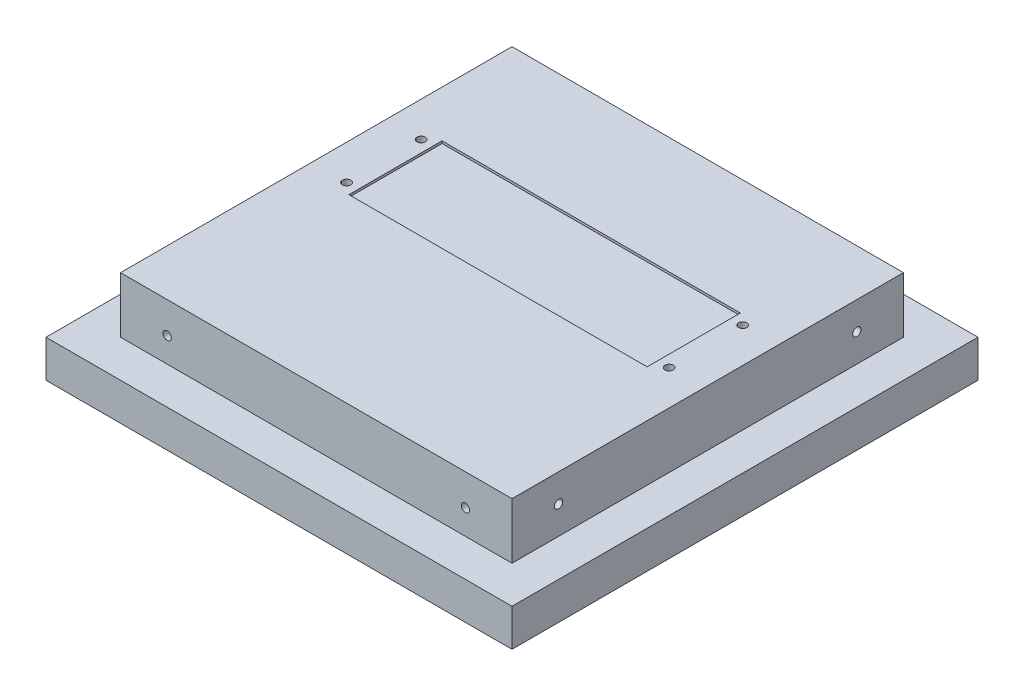
SolidWorks part; units mm, degrees
ref_plane "Front Plane" through (0, 0, 0) normal (0, 0, 1) x (1, 0, 0)
ref_plane "Top Plane" through (0, 0, 0) normal (0, 1, 0) x (1, 0, 0)
ref_plane "Right Plane" through (0, 0, 0) normal (1, 0, 0) x (0, 0, -1)
sketch "Sketch1" plane through (0, 0, 0) normal (0, 1, 0) x (1, 0, 0)
  line L1 (-50, 50) -> (50, 50)
  line L2 (-50, 50) -> (-50, -50)
  line L3 (-50, -50) -> (50, -50)
  line L4 (50, 50) -> (50, -50)
  line L5 (-50, 50) -> (50, -50) construction
  line L6 (-50, -50) -> (50, 50) construction
  point P0 (0, 0)
  dimension "D1" = 100
extrude "Boss-Extrude2" add sketch "Sketch1" along normal blind 8
sketch "Sketch2" plane through (0, 8, 0) normal (0, 1, 0) x (1, 0, 0)
  line L1 (-42, 42) -> (42, 42)
  line L2 (-42, 42) -> (-42, -42)
  line L3 (-42, -42) -> (42, -42)
  line L4 (42, 42) -> (42, -42)
  line L5 (-42, 42) -> (42, -42) construction
  line L6 (-42, -42) -> (42, 42) construction
  point P0 (0, 0)
extrude "Boss-Extrude3" add sketch "Sketch2" along normal blind 12
sketch "Sketch3" plane through (0, 20, 0) normal (0, 1, 0) x (1, 0, 0)
  line L0 (37, 37) -> (37, 32) construction
  line L1 (37, -37) -> (-37, -37)
  line L2 (37, -37) -> (37, 37)
  line L3 (37, 37) -> (-37, 37)
  line L4 (-37, -37) -> (-37, 37)
  line L5 (37, -37) -> (-37, 37) construction
  line L6 (37, 37) -> (-37, -37) construction
  line L7 (37, 32) -> (-37, 32) construction
  line L8 (-37, 32) -> (-37, 37) construction
  line L9 (37, 32) -> (37, 22) construction
  line L10 (37, 22) -> (-37, 22) construction
  line L11 (-37, 22) -> (-37, 32) construction
  line L12 (37, 22) -> (37, -8) construction
  line L13 (37, -8) -> (-37, -8) construction
  line L14 (-37, -8) -> (-37, 22) construction
  line L15 (37, -8) -> (32, -8) construction
  line L16 (32, -8) -> (32, 22) construction
  line L17 (-37, -8) -> (-32, -8) construction
  line L18 (-32, -8) -> (-32, 22) construction
  line L19 (32, -8) -> (32, -3) construction
  line L20 (32, -3) -> (-32, -3) construction
  line L21 (-32, 22) -> (-32, 17) construction
  line L22 (-32, 17) -> (32, 17) construction
  line L24 (32, -3) -> (-32, -3)
  line L25 (32, -3) -> (32, 17)
  line L26 (32, 17) -> (-32, 17)
  line L27 (-32, -3) -> (-32, 17)
  line L28 (32, 22) -> (34.5, 22) construction
  line L29 (-32, 22) -> (-34.5, 22) construction
  line L30 (34.5, -7.7713) -> (34.5, -0.7713) construction
  line L31 (34.5, 22) -> (34.5, 15) construction
  line L33 (-34.5, 22) -> (-34.5, 15) construction
  line L34 (-34.5, -8) -> (-34.5, -1) construction
  point P0 (0, 0)
extrude "Cut-Extrude1" cut sketch "Sketch3" against normal blind 0.5 contours L25 L24 L27 L26
hole_wizard "#2-56 Tapped Hole1" positions "3DSketch1" profile "Sketch4" tap size "#2-56" standard "ANSI Inch"
sketch3d "3DSketch1"
  point P0 (34.5, 20, 0.7713)
  point P3 (34.5, 20, -15)
  point P6 (-34.5, 20, -15)
  point P9 (-34.5, 20, 1)
sketch "Sketch4" plane through (34.5, 20, 0.7713) normal (1, 0, 0) x (0, 0, 1)
  line L0 (0, 0) -> (0, 15.5342)
  line L1 (0, 15.5342) -> (0.889, 15)
  line L2 (0.889, 15) -> (0.889, 0)
  line L5 (0.889, 0) -> (0, 0)
  line L10 (0, 15.5342) -> (-0.889, 15) construction
  line L11 (0, -6.35) -> (0, 107.95) construction
  dimension "Tap Drill Dia." = 1.778
  dimension "Tap Drill Depth" = 15
  dimension "Drill Angle" = 118
cosmetic thread "Hole Thread1" parameters "D1"=12, "D2"=2.1844
cosmetic thread "Hole Thread2" parameters "D1"=12, "D2"=2.1844
cosmetic thread "Hole Thread3" parameters "D1"=12, "D2"=2.1844
cosmetic thread "Hole Thread4" parameters "D1"=12, "D2"=2.1844
sketch "Sketch5" plane through (42, 0, 0) normal (1, 0, 0) x (0, 0, -1)
  line L0 (-42, 20) -> (42, 8) construction
  line L1 (42, 8) -> (42, 20) construction
  line L2 (42, 20) -> (-42, 8) construction
  line L3 (-42, 8) -> (-42, 20) construction
  line L4 (42, 14) -> (32, 14) construction
  line L5 (-42, 14) -> (-32, 14) construction
sketch "Sketch6" plane through (0, 0, -42) normal (0, 0, -1) x (-1, 0, 0)
  line L0 (-42, 20) -> (42, 8) construction
  line L1 (42, 8) -> (42, 20) construction
  line L2 (42, 20) -> (-42, 8) construction
  line L3 (-42, 8) -> (-42, 20) construction
  line L4 (-42, 14) -> (-32, 14) construction
  line L5 (42, 13.3038) -> (32, 13.3038) construction
sketch "Sketch7" plane through (-42, 0, 0) normal (-1, 0, 0) x (0, 0, 1)
  line L0 (-42, 20) -> (42, 8) construction
  line L1 (42, 8) -> (42, 20) construction
  line L2 (42, 13.3038) -> (32, 13.3038) construction
  line L3 (-42, 13.3038) -> (-32, 13.3038) construction
sketch "Sketch8" plane through (0, 0, 42) normal (0, 0, 1) x (1, 0, 0)
  line L0 (-42, 13.3038) -> (-32, 13.3038) construction
  line L1 (42, 13.3038) -> (32, 13.3038) construction
  line L2 (42, 20) -> (42, 8) construction
hole_wizard "#2-56 Tapped Hole2" positions "3DSketch2" profile "Sketch9" tap size "#2-56" standard "ANSI Inch"
sketch3d "3DSketch2"
  point P0 (-32, 13.3038, 42)
  point P3 (-42, 13.3038, 32)
  point P6 (32, 13.3038, 42)
sketch "Sketch9" plane through (-32, 13.3038, 42) normal (1, 0, 0) x (0, -1, 0)
  line L0 (0, 0) -> (0, 7.5342)
  line L1 (0, 7.5342) -> (0.889, 7)
  line L2 (0.889, 7) -> (0.889, 0)
  line L5 (0.889, 0) -> (0, 0)
  line L10 (0, 7.5342) -> (-0.889, 7) construction
  line L11 (0, -6.35) -> (0, 107.95) construction
  dimension "Tap Drill Dia." = 1.778
  dimension "Tap Drill Depth" = 7
  dimension "Drill Angle" = 118
cosmetic thread "Hole Thread5" parameters "D1"=7, "D2"=2.1844
cosmetic thread "Hole Thread6" parameters "D1"=7, "D2"=2.1844
cosmetic thread "Hole Thread7" parameters "D1"=7, "D2"=2.1844
hole_wizard "#2-56 Tapped Hole3" positions "3DSketch3" profile "Sketch10" tap size "#2-56" standard "ANSI Inch"
sketch3d "3DSketch3"
  point P0 (42, 14, 32)
  point P3 (42, 14, -32)
  point P6 (32, 14, -42)
  point P9 (-32, 13.3038, -42)
sketch "Sketch10" plane through (42, 14, 32) normal (0, 1, 0) x (0, 0, -1)
  line L0 (0, 0) -> (0, 7.5342)
  line L1 (0, 7.5342) -> (0.889, 7)
  line L2 (0.889, 7) -> (0.889, 0)
  line L5 (0.889, 0) -> (0, 0)
  line L10 (0, 7.5342) -> (-0.889, 7) construction
  line L11 (0, -6.35) -> (0, 107.95) construction
  dimension "Tap Drill Dia." = 1.778
  dimension "Tap Drill Depth" = 7
  dimension "Drill Angle" = 118
cosmetic thread "Hole Thread8" parameters "D1"=6.98, "D2"=2.1844
cosmetic thread "Hole Thread9" parameters "D1"=6.98, "D2"=2.1844
cosmetic thread "Hole Thread10" parameters "D1"=6.98, "D2"=2.1844
cosmetic thread "Hole Thread11" parameters "D1"=6.98, "D2"=2.1844
hole_wizard "#2-56 Tapped Hole4" positions "3DSketch4" profile "Sketch11" tap size "#2-56" standard "ANSI Inch"
sketch3d "3DSketch4"
  point P0 (-42, 13.3038, -32)
sketch "Sketch11" plane through (-42, 13.3038, -32) normal (0, 1, 0) x (0, 0, 1)
  line L0 (0, 0) -> (0, 7.5342)
  line L1 (0, 7.5342) -> (0.889, 7)
  line L2 (0.889, 7) -> (0.889, 0)
  line L5 (0.889, 0) -> (0, 0)
  line L10 (0, 7.5342) -> (-0.889, 7) construction
  line L11 (0, -6.35) -> (0, 107.95) construction
  dimension "Tap Drill Dia." = 1.778
  dimension "Tap Drill Depth" = 7
  dimension "Drill Angle" = 118
cosmetic thread "Hole Thread12" parameters "D1"=6.98, "D2"=2.1844
sketch "Sketch12" plane through (0, 0, 0) normal (0, -1, 0) x (-1, 0, 0)
  line L0 (50, 50) -> (-50, -50) construction
  line L1 (-50, -50) -> (-50, 0) construction
  line L2 (-50, -50) -> (-50, 50) construction
  line L3 (-50, 0) -> (50, 0) construction
  line L4 (50, 50) -> (50, -50) construction
  line L5 (50, 0) -> (50, -50) construction
  line L6 (50, -50) -> (-50, 50) construction
sketch "Sketch13" plane through (0, 0, 0) normal (0, -1, 0) x (-1, 0, 0)
  line L1 (30, 30) -> (-30, 30)
  line L2 (30, 30) -> (30, -30)
  line L3 (30, -30) -> (-30, -30)
  line L4 (-30, 30) -> (-30, -30)
  line L5 (30, 30) -> (-30, -30) construction
  line L6 (30, -30) -> (-30, 30) construction
  point P0 (0, 0)
hole_wizard "1/4-20 Tapped Hole1" positions "3DSketch5" profile "Sketch14" tap size "1/4-20" standard "ANSI Inch"
sketch3d "3DSketch5"
  point P0 (-30, 0, -30)
  point P3 (-30, 0, 30)
  point P6 (30, 0, 30)
  point P9 (30, 0, -30)
sketch "Sketch14" plane through (-30, 0, -30) normal (1, 0, 0) x (0, 0, -1)
  line L0 (0, 0) -> (0, 9.5338)
  line L1 (0, 9.5338) -> (2.5527, 8)
  line L2 (2.5527, 8) -> (2.5527, 0)
  line L5 (2.5527, 0) -> (0, 0)
  line L10 (0, 9.5338) -> (-2.5527, 8) construction
  line L11 (0, -6.35) -> (0, 107.95) construction
  dimension "Tap Drill Dia." = 5.1054
  dimension "Tap Drill Depth" = 8
  dimension "Drill Angle" = 118
cosmetic thread "Hole Thread13" parameters "D1"=7, "D2"=6.35
cosmetic thread "Hole Thread14" parameters "D1"=7, "D2"=6.35
cosmetic thread "Hole Thread15" parameters "D1"=7, "D2"=6.35
cosmetic thread "Hole Thread16" parameters "D1"=7, "D2"=6.35
